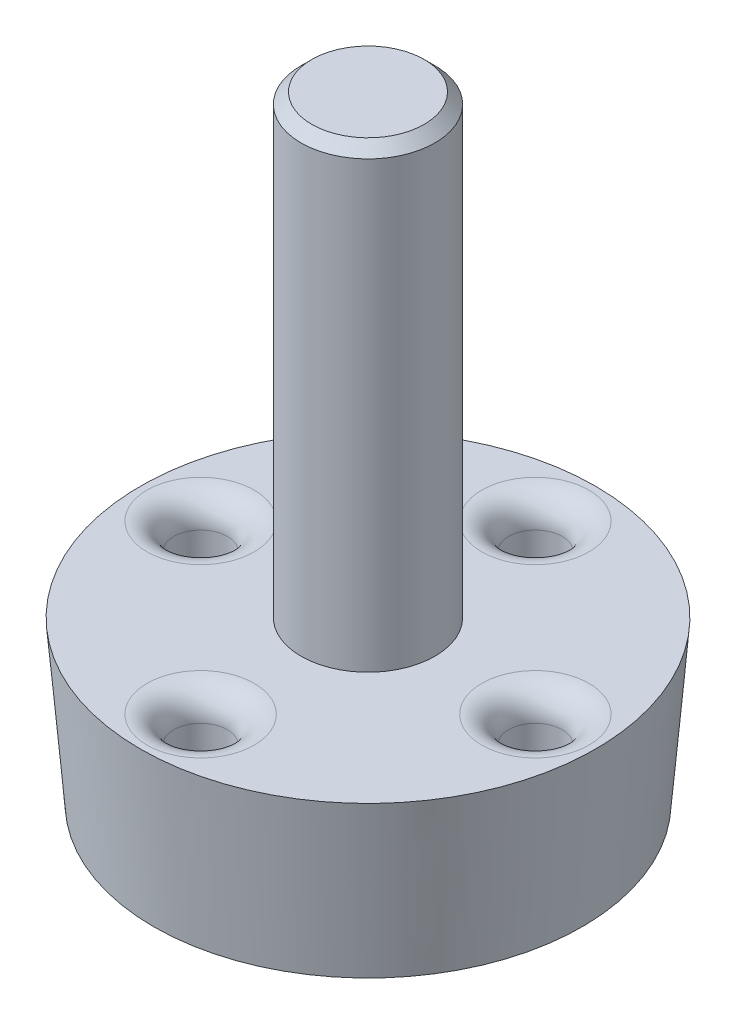
SolidWorks part; units mm, degrees
ref_plane "Front Plane" through (0, 0, 0) normal (0, 0, 1) x (1, 0, 0)
ref_plane "Top Plane" through (0, 0, 0) normal (0, 1, 0) x (1, 0, 0)
ref_plane "Right Plane" through (0, 0, 0) normal (1, 0, 0) x (0, 0, -1)
sketch "Sketch1" plane through (0, 0, 0) normal (0, 1, 0) x (1, 0, 0)
  circle A0 centre (0, 0) radius 8
  dimension "D1" = 16
ref_plane "Plane1" through (0, 6, 0) normal (0, 1, 0) x (1, 0, 0)
sketch "Sketch3" plane through (0, 6, 0) normal (0, 1, 0) x (1, 0, 0)
  circle A0 centre (0, 0) radius 8.5
  dimension "D1" = 17
loft "Loft1" add profiles "Sketch3", "Sketch1" connector at (4.7833, 6, 7.0264) connector at (4.6941, 0, 6.478)
sketch "Sketch4" plane through (0, 6, 0) normal (0, 1, 0) x (1, 0, 0)
  circle A0 centre (0, 0) radius 2.5
  dimension "D1" = 5
extrude "Boss-Extrude1" add sketch "Sketch4" along normal blind 17
sketch "Sketch5" plane through (0, 0, 0) normal (0, -1, 0) x (1, 0, 0)
  circle A0 centre (0, 0) radius 4.5
  dimension "D1" = 9
extrude "Cut-Extrude1" cut sketch "Sketch5" against normal blind 2
sketch "Sketch6" plane through (0, 0, 0) normal (0, -1, 0) x (1, 0, 0)
  circle A0 centre (0, 6.25) radius 1
  circle A2 centre (6.25, 0) radius 1
  circle A3 centre (0, -6.25) radius 1
  circle A4 centre (-6.25, 0) radius 1
  point P14 (0, 0)
  dimension "D1" = 2
  dimension "D3" = 6.25
  dimension "D2" = 4
extrude "Cut-Extrude4" cut sketch "Sketch6" against normal up to surface (6 mm away) up to face at (0, 6, 2.5)
sketch "Sketch8" plane through (0, 2, 0) normal (0, -1, 0) x (1, 0, 0)
  circle A0 centre (0, 0) radius 2
  dimension "D1" = 4
extrude "Cut-Extrude5" cut sketch "Sketch8" against normal blind 1
fillet "Fillet1" radius 1 1 edges at (0, 2, -2)
chamfer "Chamfer1" distance 0.4 angle 45 1 edges at (0, 23, 2.5)
fillet "Fillet2" radius 1 4 edges at (-6.25, 6, 1) (0, 6, 7.25) (6.25, 6, 1) (0, 6, -5.25)
